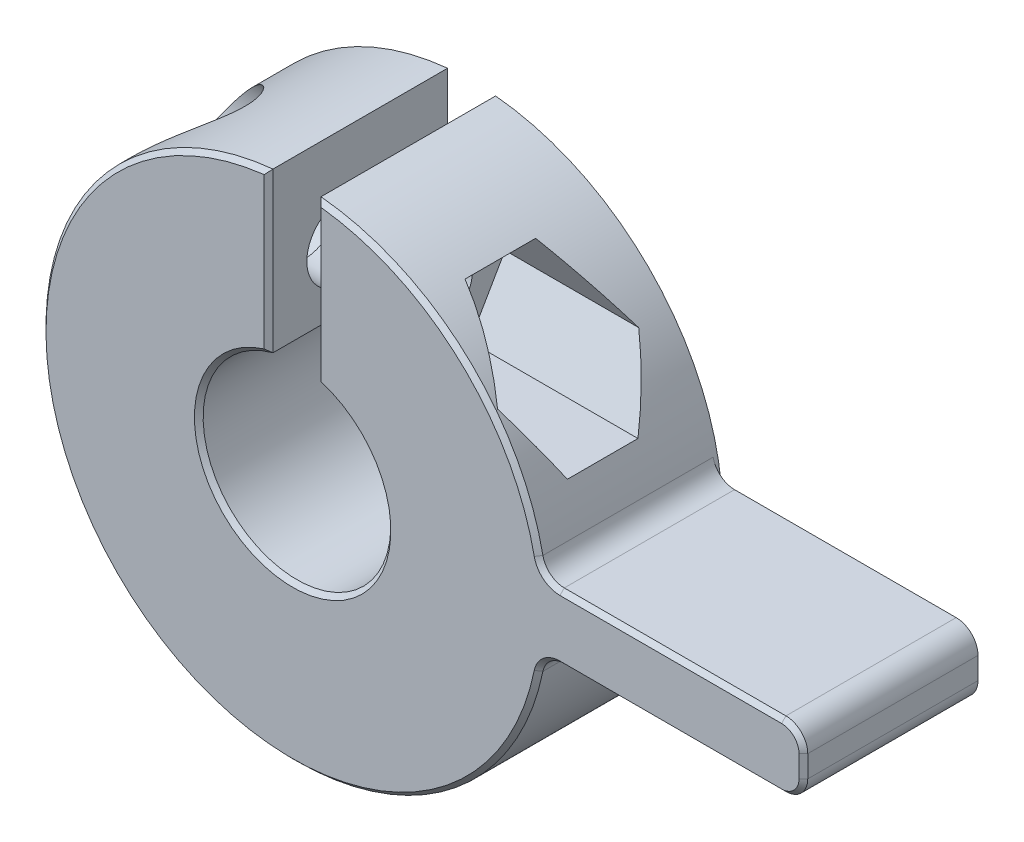
SolidWorks part; units mm, degrees
ref_plane "Front Plane" through (0, 0, 0) normal (0, 0, 1) x (1, 0, 0)
ref_plane "Top Plane" through (0, 0, 0) normal (0, 1, 0) x (1, 0, 0)
ref_plane "Right Plane" through (0, 0, 0) normal (1, 0, 0) x (0, 0, -1)
sketch "Sketch1" plane through (0, 0, 0) normal (0, 0, 1) x (1, 0, 0)
  line L0 (0, 0) -> (0, 11.5) construction
  line L1 (1.1, 0) -> (1.1, 11.4473)
  line L2 (-1.1, 0) -> (-1.1, 11.4473)
  line L3 (0, 0) -> (0, 11.5965) construction
  line L4 (1.1, 0) -> (1.1, 11.5965) construction
  line L5 (-1.1, 0) -> (-1.1, 11.5965) construction
  circle A0 centre (0, 0) radius 4.3
  circle A1 centre (0, 0) radius 11.5
  dimension "D1" = 8.6
  dimension "D2" = 23
  dimension "D3" = 1.1
  dimension "D4" = 1.1
extrude "Boss-Extrude1" add sketch "Sketch1" along normal blind 15 contours L2 A1 L1 A0 region at (1.4249, 7.8021, 0)
sketch "Sketch4" plane through (0, 0, 0) normal (1, 0, 0) x (0, 0, -1)
  line L0 (0, -11.5) -> (0, 11.4473) construction
  circle A0 centre (-11.5, 7) radius 3
  circle A1 centre (-3.5, 7) radius 3
  circle A2 centre (-3.5, 7) radius 1.75
  circle A3 centre (-11.5, 7) radius 1.75
  dimension "D1" = 6
  dimension "D5" = 3.5
  dimension "D2" = 8
  dimension "D3" = 7
  dimension "D4" = 3.5
extrude "Cut-Extrude4" cut sketch "Sketch4" against normal blind 15 from offset 3 offset against normal yes
extrude "Cut-Extrude5" cut sketch "Sketch4<2>" against normal through all both and the other way through all contours A3 | A2 region at (0, 7, 3.5) region at (0, 7, 11.5)
sketch "Sketch4<2>" plane through (0, 0, 0) normal (1, 0, 0) x (0, 0, -1) same geometry as "Sketch4"
sketch "Sketch5" plane through (0, 0, 0) normal (1, 0, 0) x (0, 0, -1)
  line L1 (-9.8834, 9.8) -> (-13.1166, 9.8)
  line L2 (-13.1166, 9.8) -> (-14.7332, 7)
  line L3 (-14.7332, 7) -> (-13.1166, 4.2)
  line L4 (-13.1166, 4.2) -> (-9.8834, 4.2)
  line L5 (-9.8834, 4.2) -> (-8.2668, 7)
  line L6 (-8.2668, 7) -> (-9.8834, 9.8)
  line L7 (-1.8834, 9.8) -> (-5.1166, 9.8)
  line L8 (-5.1166, 9.8) -> (-6.7332, 7)
  line L9 (-6.7332, 7) -> (-5.1166, 4.2)
  line L10 (-5.1166, 4.2) -> (-1.8834, 4.2)
  line L11 (-1.8834, 4.2) -> (-0.2668, 7)
  line L12 (-0.2668, 7) -> (-1.8834, 9.8)
  circle A0 centre (-11.5, 7) radius 2.8 construction
  circle A1 centre (-3.5, 7) radius 2.8 construction
  dimension "D1" = 5.6
  dimension "D2" = 5.6
extrude "Cut-Extrude6" cut sketch "Sketch5" along normal blind 15 from offset 3
sketch "Sketch6" plane through (0, 0, 0) normal (0, 0, -1) x (-1, 0, 0)
  circle A0 centre (0, 0) radius 14
  dimension "D1" = 28
extrude "Cut-Extrude7" cut sketch "Sketch6" against normal blind 6.8
sketch "Sketch7" plane through (0, 0, 15) normal (0, 0, 1) x (1, 0, 0)
  line L1 (11.4018, 1.5) -> (23.4018, 1.5)
  line L2 (11.4018, 1.5) -> (11.4018, -1.5)
  line L3 (11.4018, -1.5) -> (23.4018, -1.5)
  line L4 (23.4018, 1.5) -> (23.4018, -1.5)
  arc A0 (-1.1, 11.4473) -> (1.1, 11.4473) centre (0, 0) ccw construction
  point P4 (11.4018, 0)
  dimension "D1" = 3
  dimension "D2" = 12
extrude "Boss-Extrude2" add sketch "Sketch7" against normal blind 8
fillet "Fillet1" radius 1 4 edges at (23.4018, 1.5, 11) (23.4018, -1.5, 11) (11.4018, -1.5, 11) (11.4018, 1.5, 11)
chamfer "Chamfer1" [suppressed] distance 1 angle 45
chamfer "Chamfer2" distance 0.2 angle 45 12 edges at (0, -4.3, 15) (1.1, 7.8021, 15) (7.6914, 8.5494, 15) (-8.5494, -7.6914, 15) (-1.1, 7.8021, 15) (23.1089, -1.2071, 15) (17.3246, -1.5, 15) (11.615, -1.7254, 15) (11.615, 1.7254, 15) (17.3246, 1.5, 15) (23.1089, 1.2071, 15) (23.4018, 0, 15)
